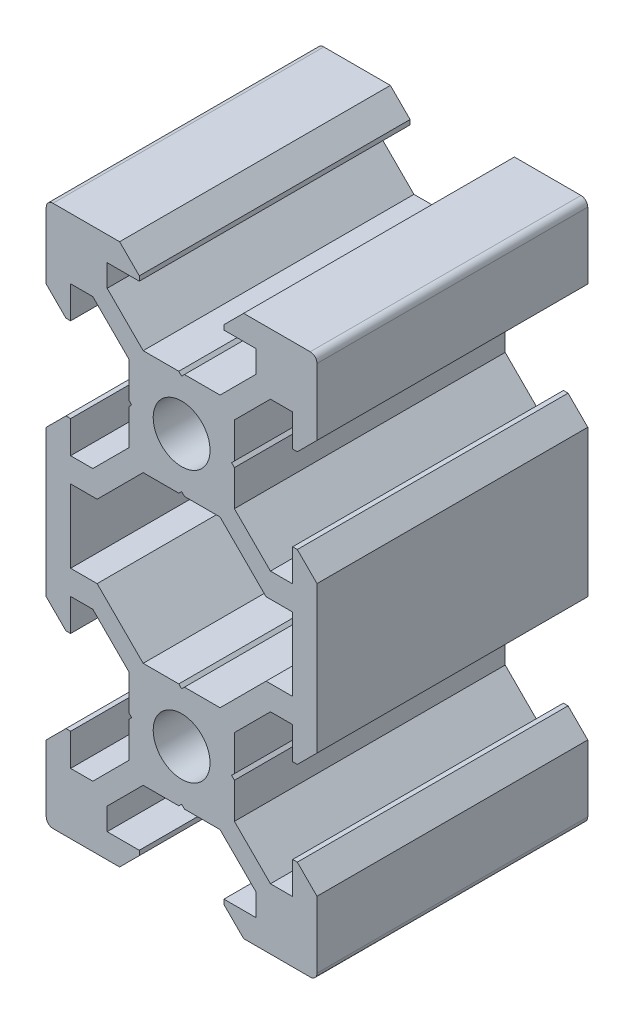
SolidWorks part; units mm, degrees
ref_plane "Plan de face" through (0, 0, 0) normal (0, 0, 1) x (1, 0, 0)
ref_plane "Plan de dessus" through (0, 0, 0) normal (0, 1, 0) x (1, 0, 0)
ref_plane "Plan de droite" through (0, 0, 0) normal (1, 0, 0) x (0, 0, -1)
ref_axis "Axe" through (0, 0, -13.782) along (0, 0, 1)
sketch "Esquisse1" plane through (0, 0, 0) normal (0, 0, 1) x (1, 0, 0)
  line L0 (0, 22.8977) -> (0, -22.8977) construction
  line L1 (-33.6074, 0) -> (33.6074, 0) construction
  line L2 (0, 0) -> (-22.2114, 22.2114) construction
  line L3 (-9.5, 10) -> (-4.58, 10)
  line L4 (-4.58, 10) -> (-3.125, 8.545)
  line L5 (-3.125, 8.545) -> (-3.125, 8.2)
  line L6 (-3.125, 8.2) -> (-5.5, 8.2)
  line L7 (-2.8393, 3.9) -> (-5.5, 6.5607)
  line L8 (-2.8393, 3.9) -> (-0.21, 3.9)
  line L9 (-5.5, 6.5607) -> (-5.5, 8.2)
  line L10 (0, 3.69) -> (0, 2.1)
  line L11 (-3.9, 2.8393) -> (-6.5607, 5.5)
  line L12 (-8.545, 3.125) -> (-8.2, 3.125)
  line L13 (-8.2, 3.125) -> (-8.2, 5.5)
  line L14 (-6.5607, 5.5) -> (-8.2, 5.5)
  line L15 (-10, 4.58) -> (-8.545, 3.125)
  line L16 (-10, 9.5) -> (-10, 4.58)
  line L17 (-0.21, 3.9) -> (0, 3.69)
  line L18 (-3.9, 2.8393) -> (-3.9, 0.21)
  line L20 (-3.9, 0.21) -> (-3.69, 0)
  line L21 (-0.21, -3.9) -> (0, -3.69)
  line L22 (0, -3.69) -> (0, -2.1)
  line L23 (-6.5607, -5.5) -> (-8.2, -5.5)
  line L24 (-2.8393, -3.9) -> (-0.21, -3.9)
  line L25 (-8.545, -3.125) -> (-8.2, -3.125)
  line L26 (-10, -4.58) -> (-8.545, -3.125)
  line L27 (-8.2, -3.125) -> (-8.2, -5.5)
  line L28 (-2.8393, -3.9) -> (-6.2393, -7.3)
  line L29 (-3.9, -2.8393) -> (-6.5607, -5.5)
  line L30 (-3.9, -2.8393) -> (-3.9, -0.21)
  line L31 (-3.9, -0.21) -> (-3.69, 0)
  line L32 (-6.2393, -7.3) -> (-8.2, -7.3)
  line L33 (-8.2, -7.3) -> (-8.2, -10)
  line L34 (-8.2, -10) -> (-10, -10)
  line L35 (-10, -10) -> (-10, -4.58)
  arc A0 (0, -2.1) -> (0, 2.1) centre (0, 0) cw
  arc A1 (-9.5, 10) -> (-10, 9.5) centre (-9.5, 9.5) ccw
  point P4 (0, 0)
  point P7 (0, 0)
  point P30 (-10, 10)
  dimension "D5" = 11
  dimension "D2" = 2.1
  dimension "D3" = 6.25
  dimension "D10" = 0.5
  dimension "D4" = 9.16
  dimension "D6" = 1.5
  dimension "D7" = 1.8
  dimension "D8" = 4.3
  dimension "D9" = 20
  dimension "D11" = 0.42
  dimension "D12" = 10
  dimension "D13" = 1.8
extrude "Boss.-Extru.1" add sketch "Esquisse1" along normal blind 20
sketch "Esquisse3" plane through (0, 0, 20) normal (0, 0, 1) x (1, 0, 0)
  line L0 (0, 0) -> (-9.8536, 9.8536) construction
  line L1 (-8.2, 8.2) -> (-8.2, 6.57)
  line L2 (-8.2, 6.57) -> (-7.54, 6.57)
  line L3 (-7.54, 6.57) -> (-6.57, 7.54)
  line L4 (-8.2, 3.125) -> (-8.2, 5.5) construction
  line L5 (-6.57, 8.2) -> (-6.57, 7.54)
  line L6 (-8.2, 8.2) -> (-6.57, 8.2)
  line L7 (-5.5, 6.5607) -> (-5.5, 8.2) construction
  arc A0 (-9.5, 10) -> (-10, 9.5) centre (-9.5, 9.5) ccw construction
  point P13 (-7.055, 7.055)
  point P14 (-6.57, 7.87)
  dimension "D1" = 1.07
extrude "Enlèv. mat.-Extru.1" [suppressed] cut sketch "Esquisse3" against normal through all
mirror "Symétrie1" about plane through (0, 3.69, 20) normal (-1, 0, 0) of "Enlèv. mat.-Extru.1", "Boss.-Extru.1"
mirror "Symétrie6" about plane through (-8.2, -10, 20) normal (0, 1, 0) of "Symétrie1", "Boss.-Extru.1"
